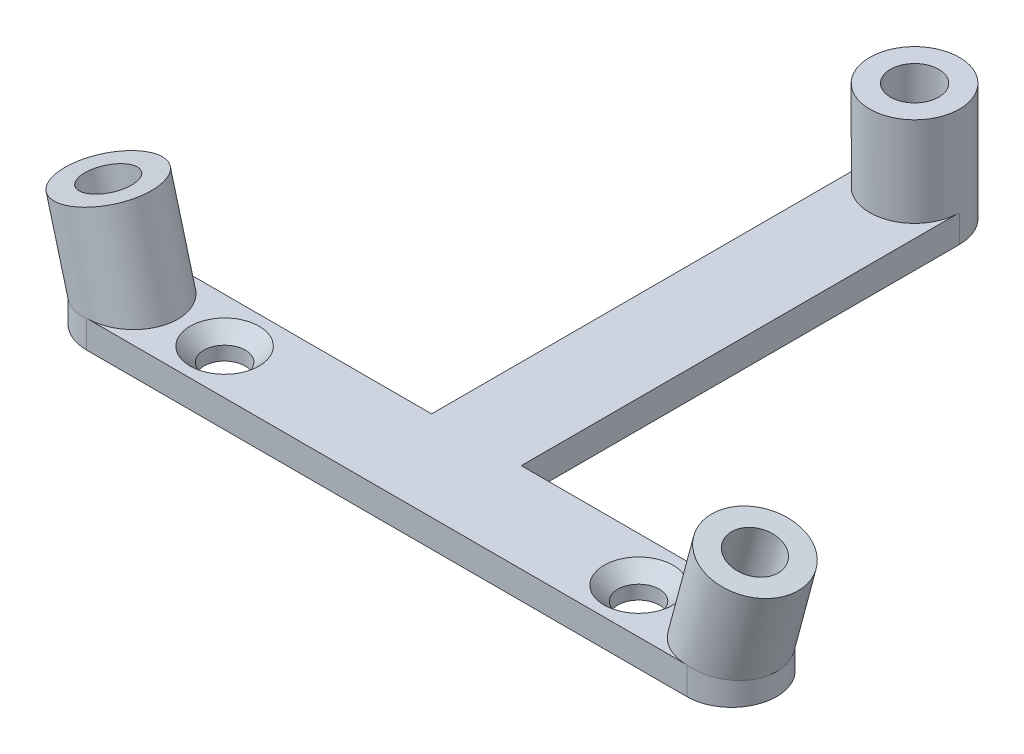
SolidWorks part; units mm, degrees
note: '?' marks a value the reader was unsure of.
ref_plane "Front Plane" through (0, 0, 0) normal (0, 0, 1) x (1, 0, 0)
ref_plane "Top Plane" through (0, 0, 0) normal (0, 1, 0) x (1, 0, 0)
ref_plane "Right Plane" through (0, 0, 0) normal (1, 0, 0) x (0, 0, -1)
ref_plane "TOP SURF" through (0, 2, 0) normal (0, 1, 0) x (1, 0, 0)
sketch "Sketch1" plane through (0, 0, 0) normal (0, 1, 0) x (1, 0, 0)
  line L0 (-25, 0) -> (25, 0) construction
  line L1 (-21.75, 0) -> (21.75, 0) construction
  line L2 (-21.75, 3.25) -> (21.75, 3.25)
  line L3 (-21.75, -3.25) -> (21.75, -3.25)
  arc A2 (-21.75, 3.25) -> (-21.75, -3.25) centre (-21.75, 0) ccw
  arc A3 (21.75, -3.25) -> (21.75, 3.25) centre (21.75, 0) ccw
  point P5 (0, 0)
  dimension "D1" = 50
  dimension "D2" = 25
  dimension "D3" = 6.5
extrude "Boss-Extrude1" add sketch "Sketch1" along normal up to surface (2 mm away) up to plane "TOP SURF"
sketch "Sketch5" plane through (0, 0, 0) normal (0, 1, 0) x (1, 0, 0)
  line L1 (-3.25, 0) -> (3.25, 0)
  line L2 (-3.25, 0) -> (-3.25, 35)
  line L3 (-3.25, 35) -> (3.25, 35) construction
  line L4 (3.25, 0) -> (3.25, 35)
  arc A0 (3.25, 35) -> (-3.25, 35) centre (0, 35) ccw
  arc A1 (-3.25, 35) -> (3.25, 35) centre (0, 35) ccw construction
  point P4 (0, 0)
  dimension "D1" = 6.5
  dimension "D2" = 35
extrude "Boss-Extrude4" add sketch "Sketch5" along normal up to surface (2 mm away) up to plane "TOP SURF"
ref_axis "Axis1" through (-21.75, 2, 3.25) along (0, 0, -1)?
ref_axis "Axis2" through (21.75, 2, 3.25) along (0, 0, -1)?
ref_axis "Axis3" through (25.0466, 2, 0) along (-1, 0, 0)?
ref_axis "Axis4" through (-3.25, 2, -35) along (1, 0, 0)?
ref_plane "STRUT1" through (-1.957, 7.3035, 0) normal (-0.2588, 0.9659, 0) x (0, 0, -1)
ref_plane "STRUT1 END" through (-3.6393, 13.582, 0) normal (-0.2588, 0.9659, 0) x (0, 0, -1)
ref_plane "STRUT2" through (1.957, 7.3035, 0) normal (0.2588, 0.9659, 0) x (0, 0, -1)
ref_plane "STRUT2 END" through (3.6393, 13.582, 0) normal (0.2588, 0.9659, 0) x (0, 0, -1)
ref_plane "Plane1" through (0, 2, 0) normal (0, 1, 0) x (1, 0, 0)
sketch "Sketch6" plane through (0, 2, 0) normal (0, 1, 0) x (1, 0, 0)
  line L0 (-3.25, 35) -> (3.25, 35) construction
  line L1 (0, -1.1) -> (0, 1.1) construction
  circle A0 centre (0, 35) radius 1.75
  circle A1 centre (0, 35) radius 3.25
  point P4 (0, 35)
  dimension "D1" = 3.5
  dimension "D2" = 1.5
extrude "Boss-Extrude5" add sketch "Sketch6" along normal blind 6.5
sketch "Sketch2" plane through (-1.957, 7.3035, 0) normal (-0.2588, 0.9659, 0) x (0, 0, -1)
  line L0 (-3.25, 20.4912) -> (3.25, 20.4912) construction
  line L1 (0, -24.7108) -> (0, 71.8817) construction
  circle A0 centre (0, 20.4912) radius 1.75
  circle A1 centre (0, 20.4912) radius 3.25
  point P0 (0, 20.4912)
  dimension "D1" = 1.5
extrude "Boss-Extrude2" add sketch "Sketch2" along normal up to surface and the other way up to surface
sketch "Sketch3" plane through (1.957, 7.3035, 0) normal (0.2588, 0.9659, 0) x (0, 0, -1)
  line L0 (-3.25, -20.4912) -> (3.25, -20.4912) construction
  line L1 (0, -23.6756) -> (0, 72.917) construction
  circle A0 centre (0, -20.4912) radius 1.75
  circle A1 centre (0, -20.4912) radius 3.25
  point P0 (0, -20.4912)
  dimension "D1" = 1.5
extrude "Boss-Extrude3" add sketch "Sketch3" along normal up to surface and the other way up to surface
sketch "Sketch4" plane through (0, 2, 0) normal (0, 1, 0) x (1, 0, 0)
  line L0 (-15, 0) -> (15, 0) construction
  line L1 (25.0466, 0) -> (-74.9534, 0) construction
  circle A0 centre (-15, 0) radius 1.5
  circle A1 centre (15, 0) radius 1.5
  point P6 (0, 0)
  dimension "D1" = 30
extrude "Cut-Extrude1" cut sketch "Sketch4" against normal up to surface (2 mm away) up to face at (0, 0, -9.9688)
chamfer "Chamfer1" distance 1 angle 45 2 edges at (15, 2, 1.5) (-15, 2, 1.5)
equation "\"WIDTH\"= 50"
equation "\"WALLTHICK\"= 1.5"
equation "\"RODDIA\"= 3.5"
equation "\"D1@Sketch1\"=\"WIDTH\""
equation "\"D2@Sketch1\"=\"WIDTH\"/2"
equation "\"D3@Sketch1\"=\"WALLTHICK\"*2 + \"RODDIA\""
equation "\"D1\"= 2"
equation "\"ANGLE\"= 30"
equation "\"D1@Sketch2\"=\"WALLTHICK\""
equation "\"D2@Sketch2\"=\"RODDIA\""
equation "\"D1@Sketch3\"=\"WALLTHICK\""
equation "\"D2@Sketch3\"=\"RODDIA\""
equation "\"SCREWSIZE\"= 3"
equation "\"D2@Sketch4\"=\"SCREWSIZE\""
equation "\"D1@Sketch5\"=\"RODDIA\"+\"WALLTHICK\"*2"
equation "\"D1@Sketch6\"=\"RODDIA\""
equation "\"D2@Sketch6\"=\"WALLTHICK\""
